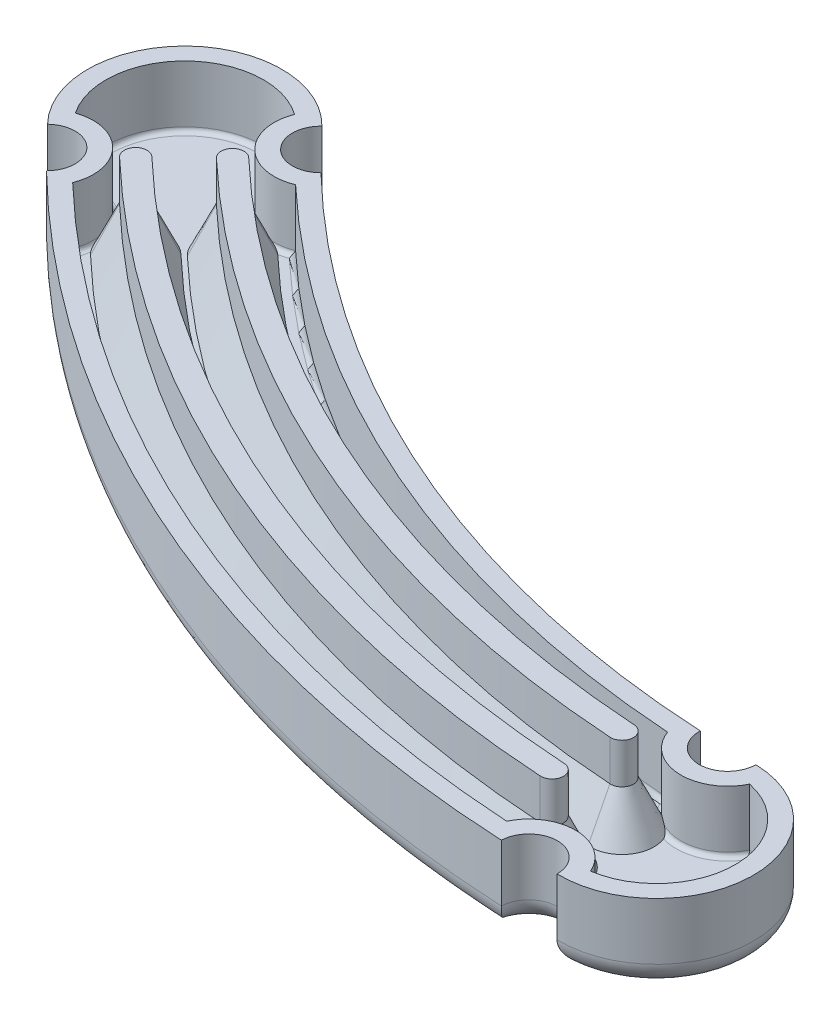
SolidWorks part; units mm, degrees
ref_plane "Front Plane" through (0, 0, 0) normal (0, 0, 1) x (1, 0, 0)
ref_plane "Top Plane" through (0, 0, 0) normal (0, 1, 0) x (1, 0, 0)
ref_plane "Right Plane" through (0, 0, 0) normal (1, 0, 0) x (0, 0, -1)
sketch "Sketch1" plane through (0, 0, 0) normal (0, 1, 0) x (1, 0, 0)
  line L0 (-71.3503, -82.2054) -> (-34958.9124, 35734.8019) construction
  line L1 (-70.1201, -59.1107) -> (-34995.8073, 35720.7213) construction
  line L2 (-39.7979, -107.5277) -> (49945.2079, -1331.9458) construction
  line L3 (31.7139, -92.3079) -> (50015.3873, -1369.9589) construction
  circle A0 centre (0, 0) radius 100 construction
  arc A1 (-0.2082, -108.4975) -> (0.2172, -91.5028) centre (0, -100) ccw
  arc A2 (-67.2386, -62.0626) -> (-79.4101, -73.9309) centre (-73.3212, -68) ccw
  arc A3 (-63.7464, -65.6403) -> (-4.7807, -91.375) centre (0, 0) ccw
  arc A4 (-75.9216, -77.5123) -> (-5.2063, -108.375) centre (0, 0) ccw
  arc A5 (-67.2386, -62.0626) -> (-63.7464, -65.6403) centre (-65.5159, -63.8743) ccw
  arc A6 (-75.9216, -77.5123) -> (-79.4101, -73.9309) centre (-77.6873, -75.7425) ccw
  arc A7 (-4.7807, -91.375) -> (0.2172, -91.5028) centre (-2.2826, -91.4715) ccw
  arc A8 (-0.2082, -108.4975) -> (-5.2063, -108.375) centre (-2.708, -108.4662) ccw
  dimension "D1" = 200
  dimension "D3" = 17
  dimension "D4" = 5
  dimension "D2" = 80
extrude "Boss-Extrude1" add sketch "Sketch1" along normal blind 7
fillet "Fillet1" radius 2 8 edges at (8.4973, 0, 100.2127) (-2.3465, 0, 93.9707) (-36.6, 0, 83.8611) (-67.3049, 0, 65.6206) (-79.2553, 0, 61.9143) (-75.8965, 0, 73.9981) (-43.4, 0, 99.4419) (-2.6467, 0, 105.967)
shell "Shell1" thickness 1.6 removed face at (-37.3691, 7, 85.6233)
sketch "Sketch2" plane through (0, 1.6, 0) normal (0, 1, 0) x (1, 0, 0)
  line L0 (-73.8794, -77.2622) -> (-63.9482, -67.6627) construction
  line L1 (-6.1264, -92.8982) -> (-6.4116, -106.7075) construction
  arc A0 (-66.7567, -70.3775) -> (-6.207, -96.8035) centre (0, 0) ccw construction
  arc A1 (-71.0708, -74.5475) -> (-6.331, -102.8022) centre (0, 0) ccw construction
  arc A2 (-71.7608, -75.2712) -> (-6.3924, -103.8003) centre (0, 0) ccw
  arc A3 (-67.4449, -71.103) -> (-6.271, -97.8015) centre (0, 0) ccw
  arc A4 (-70.3808, -73.8237) -> (-6.2695, -101.8041) centre (0, 0) ccw
  arc A5 (-66.0685, -69.6519) -> (-6.1431, -95.8056) centre (0, 0) ccw
  arc A6 (-71.7608, -75.2712) -> (-70.3808, -73.8237) centre (-71.0708, -74.5475) cw
  arc A7 (-6.3924, -103.8003) -> (-6.2695, -101.8041) centre (-6.331, -102.8022) ccw
  arc A8 (-67.4449, -71.103) -> (-66.0685, -69.6519) centre (-66.7567, -70.3775) cw
  arc A9 (-6.271, -97.8015) -> (-6.1431, -95.8056) centre (-6.207, -96.8035) ccw
  point P12 (-66.7567, -70.3775)
  point P13 (-71.0708, -74.5475)
  point P14 (-68.9138, -72.4625)
  point P29 (0, 0)
  point P30 (0, 0)
  point P31 (0, 0)
  dimension "D1" = 3
  dimension "D2" = 3
  dimension "D3" = 1
  dimension "D4" = 1
extrude "Boss-Extrude2" add sketch "Sketch2" along normal offset from surface (7.4 mm away) 2 up to face at (-37.4353, 7, 85.775) offset beyond the face yes
chamfer "Chamfer1" distance 1.8 angle 65 8 edges at (-38.4009, 1.6, 87.9876) (-67.4822, 1.6, 69.6893) (-5.2091, 1.6, 96.8675) (-39.2009, 1.6, 89.8206) (-40.7988, 1.6, 93.4818) (-71.7946, 1.6, 73.8574) (-5.3328, 1.6, 102.8637) (-41.5988, 1.6, 95.3148) first distance on face at (-37.4529, 1.6, 85.8155)
